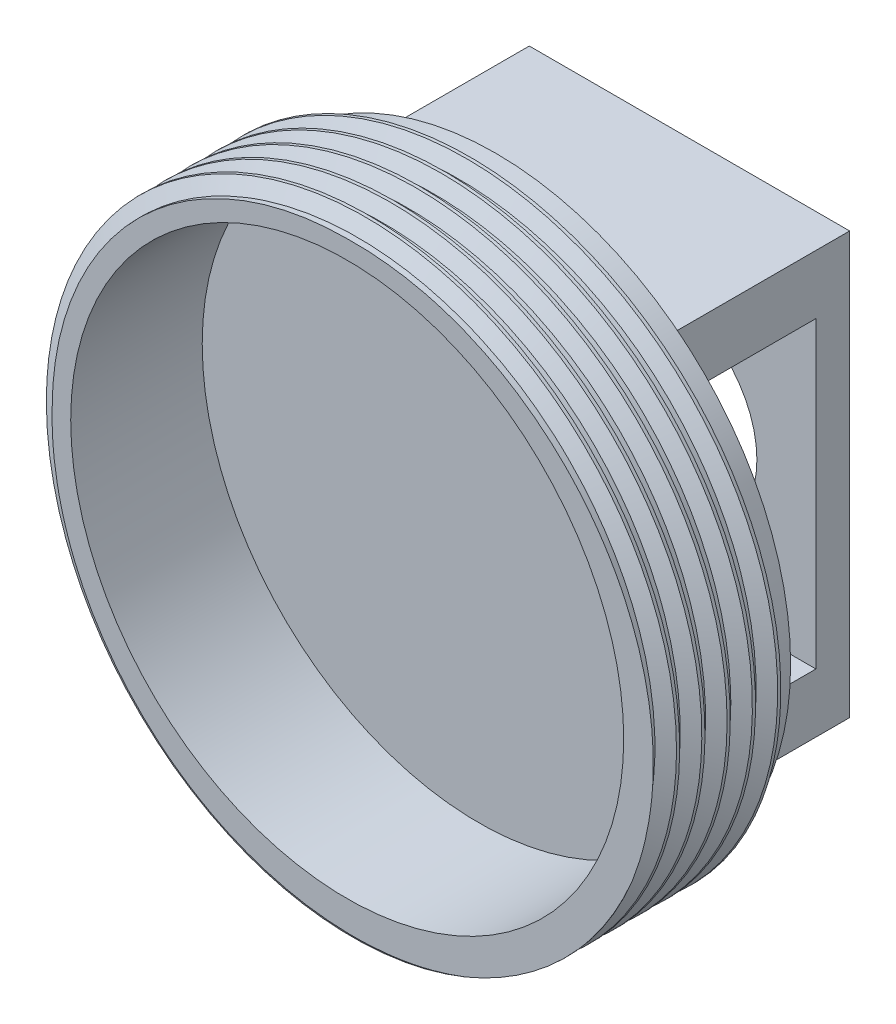
SolidWorks part; units mm, degrees
ref_plane "Piano frontale" through (0, 0, 0) normal (0, 0, 1) x (1, 0, 0)
ref_plane "Piano superiore" through (0, 0, 0) normal (0, 1, 0) x (1, 0, 0)
ref_plane "Piano destro" through (0, 0, 0) normal (1, 0, 0) x (0, 0, -1)
sketch "Schizzo1" plane through (0, 0, 0) normal (0, 0, 1) x (1, 0, 0)
  line L1 (0, 0) -> (-19, 0)
  line L2 (0, 0) -> (0, 25)
  line L3 (0, 25) -> (-19, 25)
  line L4 (-19, 0) -> (-19, 25)
  circle A0 centre (-9.5, 12.5) radius 6
  dimension "D3" = 9.5
  dimension "D4" = 12.5
  dimension "D5" = 12
  dimension "D1" = 19
  dimension "D2" = 25
extrude "Estrusione-Estrusione1" add sketch "Schizzo1" along normal blind 2
sketch "Schizzo2" plane through (0, 0, 2) normal (0, 0, 1) x (1, 0, 0)
  line L0 (-19, 25) -> (-19, 0) construction
  line L1 (-19, 21.5) -> (0, 21.5)
  line L3 (-19, 3.5) -> (0, 3.5)
  line L4 (0, 21.5) -> (0, 3.5)
  line L5 (0, 0) -> (0, 25) construction
  line L6 (-19, 0) -> (0, 0) construction
  line L8 (-19, 21.5) -> (0, 21.5)
  line L9 (-19, 21.5) -> (-19, 25)
  line L10 (-19, 25) -> (0, 25)
  line L11 (0, 21.5) -> (0, 25)
  line L12 (-19, 3.5) -> (0, 3.5)
  line L13 (-19, 3.5) -> (-19, 0)
  line L14 (-19, 0) -> (0, 0)
  line L15 (0, 3.5) -> (0, 0)
  line M12 (0, 0) -> (0, 25)
  line M13 (0, 25) -> (-19, 25)
  line M14 (-19, 25) -> (-19, 0)
  line M15 (-19, 0) -> (0, 0)
  dimension "D1" = 3.5
  dimension "D2" = 3.5
  dimension "D3" = 19
extrude "Estrusione-Estrusione2" add sketch "Schizzo2" along normal blind 9.5 contours L1 M14 M12 M13 | L3 M14 M15 M12 region at (-9.5, 23.25, 2) region at (-9.5, 1.75, 2)
sketch "Schizzo3" plane through (0, 0, 11.5) normal (0, 0, 1) x (1, 0, 0)
  circle A1 centre (-9.5, 12.5) radius 17.5
  dimension "D2" = 35
extrude "Estrusione-Estrusione3" add sketch "Schizzo3" along normal blind 1 separate body
sketch "Schizzo4" plane through (0, 0, 12.5) normal (0, 0, 1) x (1, 0, 0)
  circle A0 centre (-9.5, 12.5) radius 17.5
  circle A1 centre (-9.5, 12.5) radius 16.4
  dimension "32" = 32.8
  dimension "D2" = 35
extrude "Estrusione-Estrusione4" add sketch "Schizzo4" along normal blind 7.8
thread "Filettatura1" pitch 1.5 method extrude profile "Profilo filettatura1" start angle 0, offset 3, length 0, pitch 1.5, diameter 35
ref_plane "Piano1" through (-27, 12.5, 23.3) normal (0, -1, 0) x (-1, 0, 0)
sketch "Profilo filettatura1" plane through (-27, 12.5, 23.3) normal (0, -1, 0) x (-1, 0, 0)
  line L0 (0, 0) -> (0, 1.5) construction
  line L1 (0, 0) -> (0.8119, 0.4687)
  line L2 (0.8119, 0.4687) -> (0.8119, 0.6562)
  line L3 (0.8119, 0.6562) -> (0, 1.125)
  line L4 (0.8119, 0.5625) -> (0, 0.5625) construction
  line L11 (0, 0) -> (0, 1.125)
  point P2 (0, 0)
  dimension "Pitch" = 1.5
  dimension "Profile_Angle" = 60
  dimension "Profile_Land" = 0.1875
  dimension "Profile_Height" = 0.8119
sketch "Schizzo8" plane through (0, 0, 20.3) normal (0, 0, 1) x (1, 0, 0)
  circle A0 centre (-9.5, 12.5) radius 23.1654
extrude "Taglio-Estrusione1" cut sketch "Schizzo8" along normal blind 8
